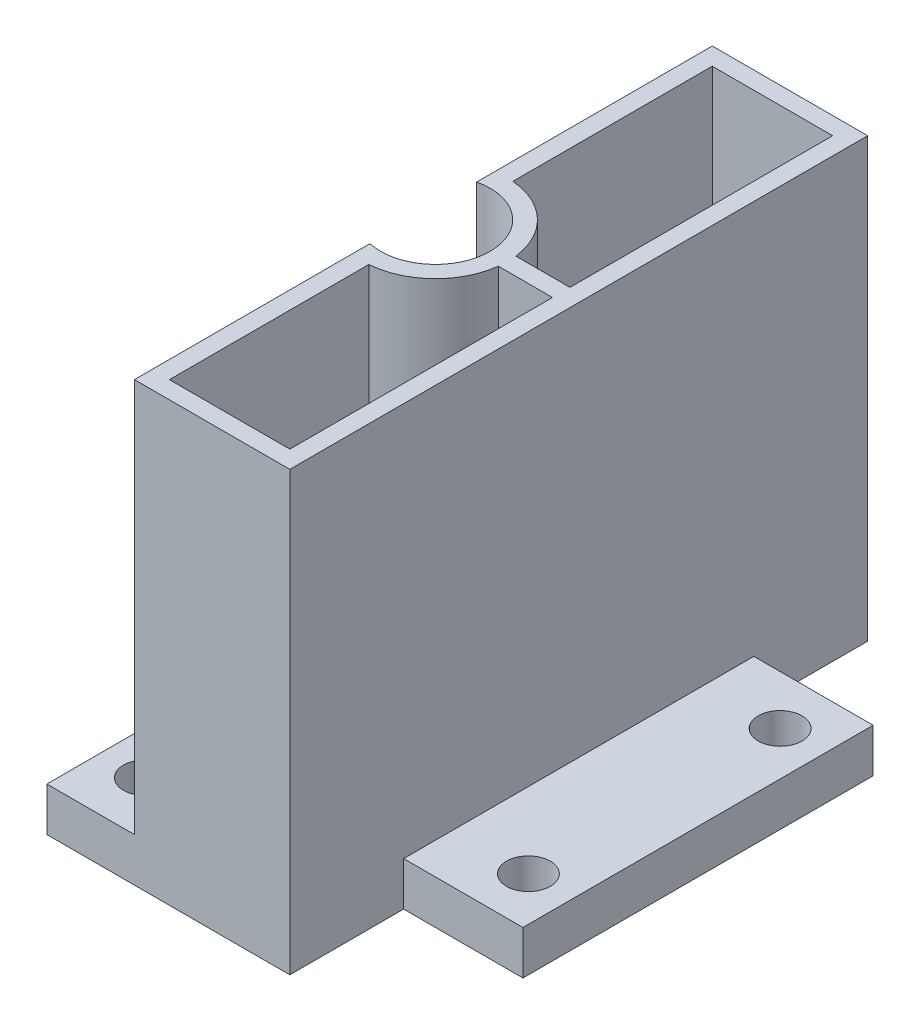
SolidWorks part; units mm, degrees
ref_plane "Front Plane" through (0, 0, 0) normal (0, 0, 1) x (1, 0, 0)
ref_plane "Top Plane" through (0, 0, 0) normal (0, 1, 0) x (1, 0, 0)
ref_plane "Right Plane" through (0, 0, 0) normal (1, 0, 0) x (0, 0, -1)
sketch "Sketch1" plane through (0, 0, 0) normal (0, 1, 0) x (1, 0, 0)
  line L0 (-0.9066, 2.4387) -> (-0.9066, 13.2)
  line L1 (6.1934, -8) -> (6.1934, 8)
  line L2 (6.1934, -8) -> (11.6434, -8)
  line L3 (11.6434, -8) -> (11.6434, 8)
  line L4 (6.1934, 8) -> (11.6434, 8)
  line L5 (-0.9066, -13.2) -> (-0.9066, -2.4387)
  line L6 (-0.9066, -13.2) -> (6.1934, -13.2)
  line L7 (6.1934, -13.2) -> (6.1934, 13.2)
  line L8 (-0.9066, 13.2) -> (6.1934, 13.2)
  line L9 (-0.1066, -12.4) -> (-0.1066, -3.2905)
  line L10 (-0.1066, -12.4) -> (5.3934, -12.4)
  line L11 (5.3934, -12.4) -> (5.3934, -0.4)
  line L12 (2.9191, -0.4) -> (5.3934, -0.4)
  line L13 (5.3934, 0.4) -> (5.3934, 12.4)
  line L14 (5.3934, 0.4) -> (2.9191, 0.4)
  line L15 (-0.1066, 3.2905) -> (-0.1066, 12.4)
  line L16 (5.3934, 12.4) -> (-0.1066, 12.4)
  line L17 (6.1934, 0) -> (-11.6434, 0) construction
  line L18 (-0.9066, 13.2) -> (-4.9066, 13.2)
  line L19 (-0.9066, 13.2) -> (-0.9066, 3.2)
  line L20 (-0.9066, 3.2) -> (-4.9066, 3.2)
  line L21 (-4.9066, 13.2) -> (-4.9066, 3.2)
  line L22 (-0.9066, -13.2) -> (-4.9066, -13.2)
  line L23 (-0.9066, -13.2) -> (-0.9066, -3.2)
  line L24 (-0.9066, -3.2) -> (-4.9066, -3.2)
  line L25 (-4.9066, -13.2) -> (-4.9066, -3.2)
  circle A0 centre (9.6434, -5.75) radius 1
  circle A1 centre (9.6434, 5.75) radius 1
  arc A2 (-0.9066, -2.4387) -> (-0.9066, 2.4387) centre (-0.3566, 0) ccw
  arc A3 (-0.1066, -3.2905) -> (2.9191, -0.4) centre (-0.3566, 0) ccw
  arc A4 (2.9191, 0.4) -> (-0.1066, 3.2905) centre (-0.3566, 0) ccw
  circle A5 centre (-2.9066, 5.7) radius 1
  circle A6 centre (-2.9066, 10.7) radius 1
  circle A7 centre (-2.9066, -5.7) radius 1
  circle A8 centre (-2.9066, -10.7) radius 1
  dimension "D1" = 4
  dimension "D2" = 4
  dimension "D3" = 10
  dimension "D4" = 10
extrude "Boss-Extrude1" add sketch "Sketch1" along normal blind 20 contours L17 L7 L8 L0 A2 L14 A4 L15 L16 L13 | L1 L17 A2 L5 L6 L7 L9 A3 L12 L11 L10 region at (-0.7567, 0, -2.8194) region at (4.1684, 0, 0.1499)
extrude "Boss-Extrude2" add sketch "Sketch1<3>" along normal blind 2 contours L4 L7 L1 L2 L3 A1 A0 | L18 L21 L20 L0 A6 A5 | L25 L22 L5 L24 A7 A8 region at (-2.9066, 0, -8.2) region at (-2.9066, 0, 8.2) region at (8.8621, 0, 0)
sketch "Sketch1<3>" plane through (0, 0, 0) normal (0, 1, 0) x (1, 0, 0) same geometry as "Sketch1"
